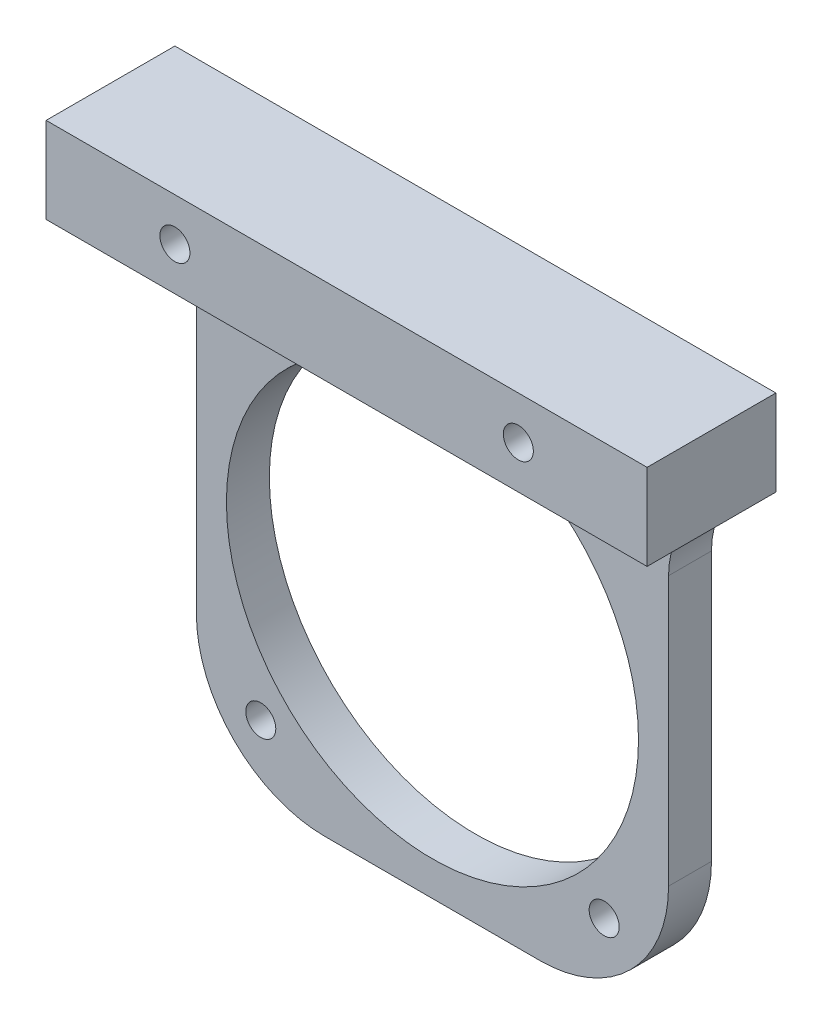
SolidWorks part; units mm, degrees
ref_plane "Plan de face" through (0, 0, 0) normal (0, 0, 1) x (1, 0, 0)
ref_plane "Plan de dessus" through (0, 0, 0) normal (0, 1, 0) x (1, 0, 0)
ref_plane "Plan de droite" through (0, 0, 0) normal (1, 0, 0) x (0, 0, -1)
sketch "Esquisse1" plane through (0, 0, 0) normal (0, 0, 1) x (1, 0, 0)
  line L0 (-20, 20) -> (20, 20) construction
  line L1 (-20, -20) -> (-20, 20) construction
  line L2 (-20, -20) -> (20, -20) construction
  line L3 (20, -20) -> (20, 20) construction
  line L5 (-27.5, 28) -> (27.5, 28)
  line L6 (-27.5, 28) -> (-27.5, -28)
  line L7 (-27.5, -28) -> (27.5, -28)
  line L8 (27.5, 28) -> (27.5, -28)
  line L9 (-35, 38) -> (35, 38)
  line L10 (-35, 38) -> (-35, 28)
  line L11 (-35, 28) -> (35, 28)
  line L12 (35, 38) -> (35, 28)
  circle A0 centre (0, 0) radius 24
  circle A1 centre (22.4239, 50.762) radius 2.0588
  circle A2 centre (-20, 20) radius 1.75
  circle A3 centre (20, 20) radius 1.75
  circle A4 centre (20, -20) radius 1.75
  circle A5 centre (-20, -20) radius 1.75
  point P17 (0, 28)
  point P18 (-27.5, 0)
  point P19 (0, 28)
  dimension "D1" = 48
  dimension "D9" = 3.5
  dimension "D10" = 3.5
  dimension "D11" = 3.5
  dimension "D12" = 3.5
  dimension "D2" = 40
  dimension "D3" = 40
  dimension "D4" = 40
  dimension "D5" = 90
  dimension "D6" = 90
  dimension "D7" = 20
  dimension "D8" = 20
  dimension "D13" = 55
  dimension "D14" = 56
  dimension "D15" = 10
  dimension "D16" = 70
extrude "Boss.-Extru.1" add sketch "Esquisse1" along normal blind 5 contours L8 L5 L6 L7 A5 A4 A3 A2 A0 | L12 L9 L10 L11 L5 region at (0, 33, 0) region at (0, 27.2151, 0)
fillet "Congé1" radius 15 2 edges at (-27.5, -28, 2.5) (27.5, -28, 2.5)
sketch "Esquisse2" plane through (0, 0, 5) normal (0, 0, 1) x (1, 0, 0)
  line L0 (-35, 38) -> (35, 38) construction
  line L1 (-35, 38) -> (35, 38)
  line L2 (-35, 38) -> (-35, 28)
  line L3 (-35, 28) -> (35, 28)
  line L4 (35, 38) -> (35, 28)
  line L5 (-35, 38) -> (-35, 28) construction
extrude "Boss.-Extru.2" add sketch "Esquisse2" along normal blind 10
sketch "Esquisse3" plane through (0, 0, 15) normal (0, 0, 1) x (1, 0, 0)
  line L0 (-35, 38) -> (-35, 28) construction
  line L1 (-35, 33) -> (35, 33) construction
  line L2 (35, 28) -> (35, 38) construction
  line L3 (-35, 28) -> (35, 28) construction
  circle A0 centre (-20, 33) radius 1.75
  circle A1 centre (20, 33) radius 1.75
  point P6 (0, 0)
  dimension "D1" = 3.5
  dimension "D2" = 3.5
  dimension "D3" = 5
  dimension "D4" = 15
  dimension "D5" = 15
extrude "Enlèv. mat.-Extru.1" cut sketch "Esquisse3" against normal blind 26
sketch "Esquisse4" plane through (0, 0, 0) normal (0, 0, -1) x (-1, 0, 0)
  line L0 (35, 38) -> (-35, 38) construction
  line L1 (-16.7091, 33) -> (-18.3546, 35.85)
  line L2 (-18.3546, 35.85) -> (-21.6454, 35.85)
  line L3 (-21.6454, 35.85) -> (-23.2909, 33)
  line L4 (-23.2909, 33) -> (-21.6454, 30.15)
  line L5 (-21.6454, 30.15) -> (-18.3546, 30.15)
  line L6 (-18.3546, 30.15) -> (-16.7091, 33)
  line L7 (16.7091, 33) -> (18.3546, 30.15)
  line L8 (18.3546, 30.15) -> (21.6454, 30.15)
  line L9 (21.6454, 30.15) -> (23.2909, 33)
  line L10 (23.2909, 33) -> (21.6454, 35.85)
  line L11 (21.6454, 35.85) -> (18.3546, 35.85)
  line L12 (18.3546, 35.85) -> (16.7091, 33)
  circle A0 centre (-20, 33) radius 2.85 construction
  circle A1 centre (20, 33) radius 2.85 construction
  dimension "D1" = 5.7
  dimension "D2" = 5.7
extrude "Enlèv. mat.-Extru.2" cut sketch "Esquisse4" against normal blind 2
fillet "Congé2" radius 10 2 edges at (-27.5, 28, 2.5) (27.5, 28, 2.5)
